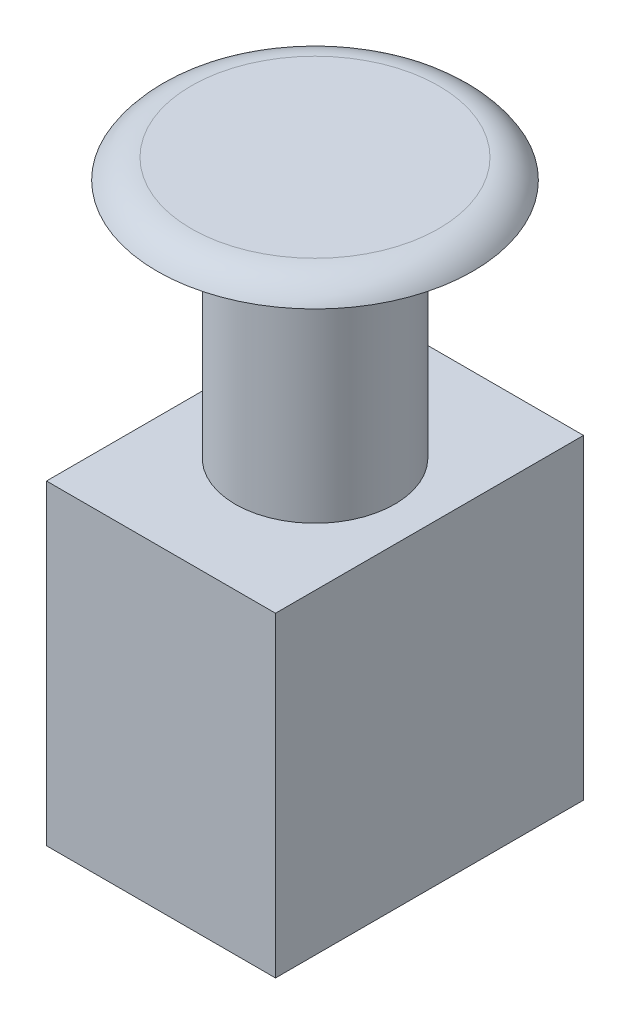
SolidWorks part; units mm, degrees
ref_plane "Front Plane" through (0, 0, 0) normal (0, 0, 1) x (1, 0, 0)
ref_plane "Top Plane" through (0, 0, 0) normal (0, 1, 0) x (1, 0, 0)
ref_plane "Right Plane" through (0, 0, 0) normal (1, 0, 0) x (0, 0, -1)
sketch "Sketch1" plane through (0, 0, 0) normal (0, 1, 0) x (1, 0, 0)
  line L1 (-14.5, 19.5) -> (14.5, 19.5)
  line L2 (-14.5, 19.5) -> (-14.5, -19.5)
  line L3 (-14.5, -19.5) -> (14.5, -19.5)
  line L4 (14.5, 19.5) -> (14.5, -19.5)
  point P4 (-14.5, 0)
  point P5 (0, -19.5)
  dimension "D1" = 39
  dimension "D2" = 29
extrude "Boss-Extrude1" add sketch "Sketch1" along normal blind 40 contours L2 L3 L4 L1
sketch "Sketch2" plane through (0, 40, 0) normal (0, 1, 0) x (1, 0, 0)
  circle A0 centre (0, 0) radius 10.1
  dimension "D1" = 20.2
extrude "Boss-Extrude2" add sketch "Sketch2" along normal blind 33
sketch "Sketch3" plane through (0, 73, 0) normal (0, 1, 0) x (1, 0, 0)
  circle A0 centre (0, 0) radius 20
  dimension "D1" = 40
extrude "Boss-Extrude3" add sketch "Sketch3" against normal blind 2.5
fillet "Fillet1" radius 5 1 edges at (0, 73, 20)
